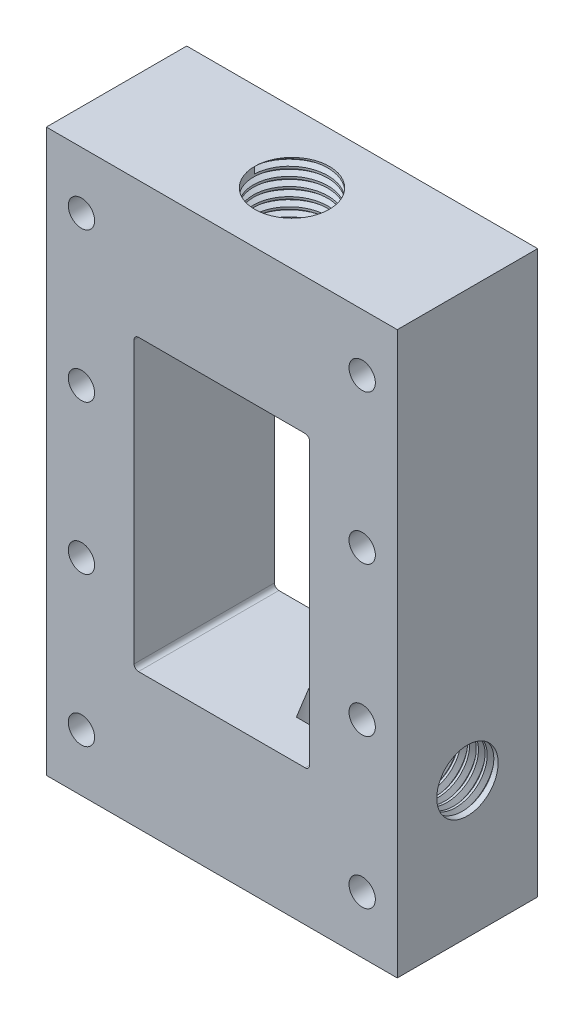
SolidWorks part; units mm, degrees
material "6061 Alloy"
ref_plane "Front Plane" through (0, 0, 0) normal (0, 0, 1) x (1, 0, 0)
ref_plane "Top Plane" through (0, 0, 0) normal (0, 1, 0) x (1, 0, 0)
ref_plane "Right Plane" through (0, 0, 0) normal (1, 0, 0) x (0, 0, -1)
sketch "Sketch2" plane through (0, 0, 0) normal (0, 0, 1) x (1, 0, 0)
  line L1 (-24.3258, 57.0505) -> (15.6742, 57.0505)
  line L2 (-24.3258, 57.0505) -> (-24.3258, -6.9495)
  line L3 (-24.3258, -6.9495) -> (15.6742, -6.9495)
  line L4 (15.6742, 57.0505) -> (15.6742, -6.9495)
  line L5 (-13.8258, 41.5505) -> (5.1742, 41.5505)
  line L6 (-14.3258, 41.0505) -> (-14.3258, 9.0505)
  line L7 (-13.8258, 8.5505) -> (5.1742, 8.5505)
  line L8 (5.6742, 41.0505) -> (5.6742, 9.0505)
  arc A0 (5.1742, 41.5505) -> (5.6742, 41.0505) centre (5.1742, 41.0505) cw
  arc A1 (5.6742, 9.0505) -> (5.1742, 8.5505) centre (5.1742, 9.0505) cw
  arc A2 (-13.8258, 8.5505) -> (-14.3258, 9.0505) centre (-13.8258, 9.0505) cw
  arc A3 (-14.3258, 41.0505) -> (-13.8258, 41.5505) centre (-13.8258, 41.0505) cw
  point P12 (5.6742, 8.5505)
  point P15 (-14.3258, 8.5505)
  point P18 (-14.3258, 41.5505)
  dimension "D7" = 0.5
  dimension "D1" = 64
  dimension "D2" = 40
  dimension "D3" = 20
  dimension "D4" = 10
  dimension "D5" = 33
  dimension "D6" = 15.5
extrude "Boss-Extrude1" add sketch "Sketch2" along normal blind 16
sketch "Sketch3" plane through (0, 0, 16) normal (0, 0, 1) x (1, 0, 0)
  line L0 (-20.3258, 50.5505) -> (-20.3258, -0.4495)
  line L1 (-24.3258, 57.0505) -> (-24.3258, -6.9495) construction
  line L2 (15.6742, 57.0505) -> (-24.3258, 57.0505) construction
  line L3 (11.6742, 50.5505) -> (11.6742, -0.4495)
  circle A0 centre (-20.3258, 50.5505) radius 1.5
  circle A1 centre (-20.3258, 33.5505) radius 1.5
  circle A2 centre (-20.3258, 16.5505) radius 1.5
  circle A3 centre (-20.3258, -0.4495) radius 1.5
  circle A4 centre (11.6742, -0.4495) radius 1.5
  circle A5 centre (11.6742, 16.5505) radius 1.5
  circle A6 centre (11.6742, 33.5505) radius 1.5
  circle A7 centre (11.6742, 50.5505) radius 1.5
  point P2 (-20.3258, 33.5505)
  point P3 (-20.3258, 16.5505)
  point P10 (11.6742, 33.5505)
  point P11 (11.6742, 16.5505)
  dimension "D1" = 4
  dimension "D2" = 17
  dimension "D3" = 6.5
  dimension "D4" = 17
  dimension "D5" = 17
  dimension "D6" = 6.5
  dimension "D7" = 32
  dimension "D8" = 17
  dimension "D9" = 17
  dimension "D10" = 17
extrude "Cut-Extrude2" cut sketch "Sketch3" against normal through all both and the other way through all contours L3 A6 | L3 A6 | A7 | A4 | A3 | L0 A2 | L0 A2 | L0 A1 | L0 A1 | A0 | L3 A5 | L3 A5 | A5 region at (-19.2952, 0.5812, 16) region at (-19.6892, 16.5505, 16) region at (-20.9625, 16.5505, 16) region at (-19.6892, 33.5505, 16) region at (-20.9625, 33.5505, 16) region at (-21.3565, 51.5812, 16) region at (12.7048, 0.5812, 16) region at (12.3108, 16.5505, 16) region at (11.0375, 16.5505, 16) region at (12.3108, 33.5505, 16) region at (11.0375, 33.5505, 16) region at (10.6435, 51.5812, 16)
sketch "Sketch5" plane through (15.6742, 0, 0) normal (1, 0, 0) x (0, 0, -1)
  line L0 (0, -6.9495) -> (0, 57.0505) construction
  line L2 (-16, -6.9495) -> (0, -6.9495) construction
  point P0 (-8, 8.5505)
  dimension "D1" = 8
  dimension "D2" = 15.5
hole_wizard "M8x1.0 Tapped Hole1" positions "Sketch5" profile "Sketch6" tap size "M8x1.0" standard "ISO"
sketch "Sketch6" plane through (15.6742, 8.5505, 8) normal (0, 1, 0) x (0, 0, -1)
  line L0 (0, 0) -> (0, 18.103)
  line L1 (0, 18.103) -> (3.5, 16)
  line L2 (3.5, 16) -> (3.5, 0)
  line L5 (3.5, 0) -> (0, 0)
  line L10 (0, 18.103) -> (-3.5, 16) construction
  line L11 (0, -6.35) -> (0, 107.95) construction
  dimension "Tap Drill Dia." = 7
  dimension "Tap Drill Depth" = 16
  dimension "Drill Angle" = 118
cosmetic thread "Hole Thread1" parameters "D1"=16, "D2"=8
thread "Thread3" pitch 1 method cut profile "Thread Profile3" start angle 0, offset 0, length 10, pitch 1, diameter 7
ref_plane "Plane3" through (15.6742, 8.5505, 11.5) normal (0, -1, 0) x (0, 0, 1)
sketch "Thread Profile3" plane through (15.6742, 8.5505, 11.5) normal (0, -1, 0) x (0, 0, 1)
  line L0 (0, 0) -> (0, 1) construction
  line L1 (0, 0) -> (0.5413, 0.3125)
  line L2 (0.5413, 0.3125) -> (0.5413, 0.4375)
  line L3 (0.5413, 0.4375) -> (0, 0.75)
  line L4 (0.5413, 0.375) -> (0, 0.375) construction
  line L11 (0, 0) -> (0, 0.75)
  point P2 (0, 0)
  dimension "Pitch" = 1
  dimension "Profile_Angle" = 60
  dimension "Profile_Land" = 0.125
  dimension "Profile_Height" = 0.5413
sketch "Sketch14" plane through (0, 57.0505, 0) normal (0, 1, 0) x (1, 0, 0)
  line L0 (15.6742, -16) -> (15.6742, 0) construction
  line L2 (15.6742, -16) -> (-24.3258, -16) construction
  point P0 (-4.3258, -8)
  dimension "D1" = 20
  dimension "D2" = 8
hole_wizard "M10 Tapped Hole1" positions "Sketch14" profile "Sketch15" tap size "M10" standard "ISO"
cosmetic thread "Hole Thread2" parameters "D1"=20, "D2"=10
sketch "Sketch15" plane through (-4.3258, 57.0505, 8) normal (1, 0, 0) x (0, 0, 1)
  line L0 (0, 0) -> (0, 13.5537)
  line L1 (0, 13.5537) -> (4.25, 11)
  line L2 (4.25, 11) -> (4.25, 0)
  line L5 (4.25, 0) -> (0, 0)
  line L10 (0, 13.5537) -> (-4.25, 11) construction
  line L11 (0, -6.35) -> (0, 107.95) construction
  dimension "Tap Drill Dia." = 8.5
  dimension "Tap Drill Depth" = 11
  dimension "Drill Angle" = 118
thread "Thread5" pitch 1 method cut profile "Thread Profile5" start angle 0, offset 0, length 11, pitch 1, diameter 8.5
ref_plane "Plane5" through (-8.5758, 57.0505, 8) normal (0, 0, 1) x (-1, 0, 0)
sketch "Thread Profile5" plane through (-8.5758, 57.0505, 8) normal (0, 0, 1) x (-1, 0, 0)
  line L0 (0, 0) -> (0, 1) construction
  line L1 (0, 0) -> (0.5413, 0.3125)
  line L2 (0.5413, 0.3125) -> (0.5413, 0.4375)
  line L3 (0.5413, 0.4375) -> (0, 0.75)
  line L4 (0.5413, 0.375) -> (0, 0.375) construction
  line L11 (0, 0) -> (0, 0.75)
  point P2 (0, 0)
  dimension "Pitch" = 1
  dimension "Profile_Angle" = 60
  dimension "Profile_Land" = 0.125
  dimension "Profile_Height" = 0.5413
